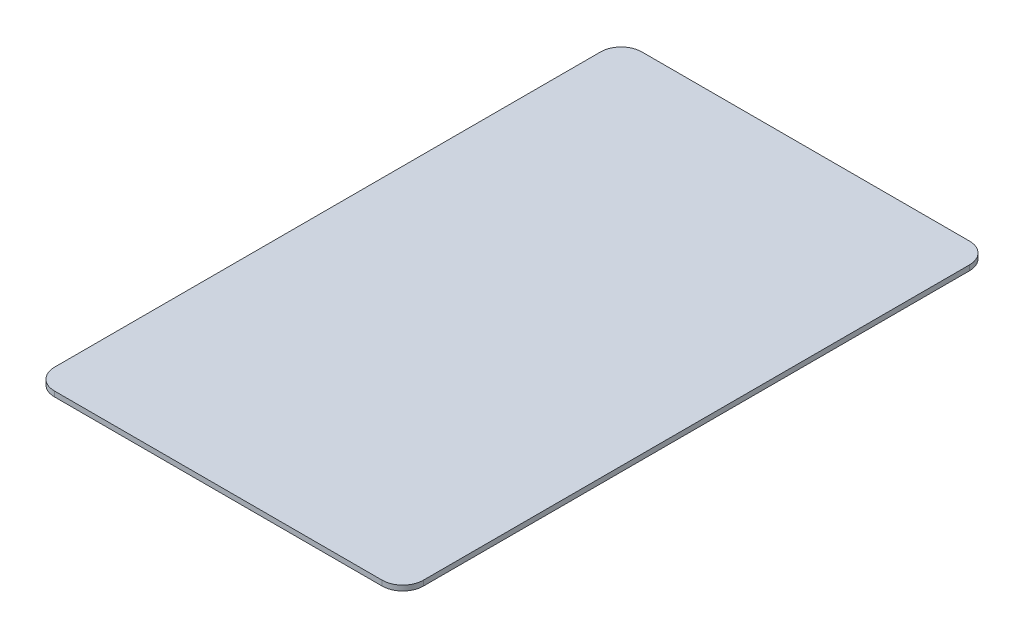
SolidWorks part; units mm, degrees
material "Acrylic (Medium-high impact)"
ref_plane "Front Plane" through (0, 0, 0) normal (0, 0, 1) x (1, 0, 0)
ref_plane "Top Plane" through (0, 0, 0) normal (0, 1, 0) x (1, 0, 0)
ref_plane "Right Plane" through (0, 0, 0) normal (1, 0, 0) x (0, 0, -1)
sketch "Sketch1" plane through (0, 0, 0) normal (0, 1, 0) x (1, 0, 0)
  line L1 (25, -31.5) -> (-25, -31.5)
  line L2 (25, -31.5) -> (25, 31.5)
  line L3 (25, 31.5) -> (-25, 31.5)
  line L4 (-25, -31.5) -> (-25, 31.5)
  line L5 (25, -31.5) -> (-25, 31.5) construction
  line L6 (25, 31.5) -> (-25, -31.5) construction
  line L7 (23, -29.5) -> (-23, -29.5)
  line L8 (23, -29.5) -> (23, 29.5)
  line L9 (23, 29.5) -> (-23, 29.5)
  line L10 (-23, -29.5) -> (-23, 29.5)
  line L11 (23, -29.5) -> (-23, 29.5) construction
  line L12 (23, 29.5) -> (-23, -29.5) construction
  point P0 (0, 0)
  point P6 (0, 0)
  dimension "D1" = 50
  dimension "D2" = 63
  dimension "D3" = 2
  dimension "D4" = 2
sketch "Sketch3" plane through (0, 0, 0) normal (0, 1, 0) x (1, 0, 0)
  line L0 (15.9, -28.5) -> (-15.9, -28.5)
  line L5 (17.9, -26.5) -> (17.9, 26.5)
  line L7 (15.9, 28.5) -> (-15.9, 28.5)
  line L8 (-17.9, -26.5) -> (-17.9, 26.5)
  line L9 (17.9, -28.5) -> (-17.9, 28.5) construction
  line L11 (17.9, 28.5) -> (-17.9, -28.5) construction
  arc A11 (-15.9, -28.5) -> (-17.9, -26.5) centre (-15.9, -26.5) cw
  arc A12 (15.9, -28.5) -> (17.9, -26.5) centre (15.9, -26.5) ccw
  arc A13 (17.9, 26.5) -> (15.9, 28.5) centre (15.9, 26.5) ccw
  arc A14 (-15.9, 28.5) -> (-17.9, 26.5) centre (-15.9, 26.5) ccw
  point P0 (0, 0)
  point P17 (0, 0)
  point P18 (0, 0)
  point P19 (-15.9, 28.5)
  dimension "D2" = 35.8
  dimension "D1" = 2
  dimension "D3" = 57
extrude "Boss-Extrude1" add sketch "Sketch3" along normal blind 0.5 contours L7 A14 L8 A11 L0 A12 L5 A13 region at (0, 0, 0)
